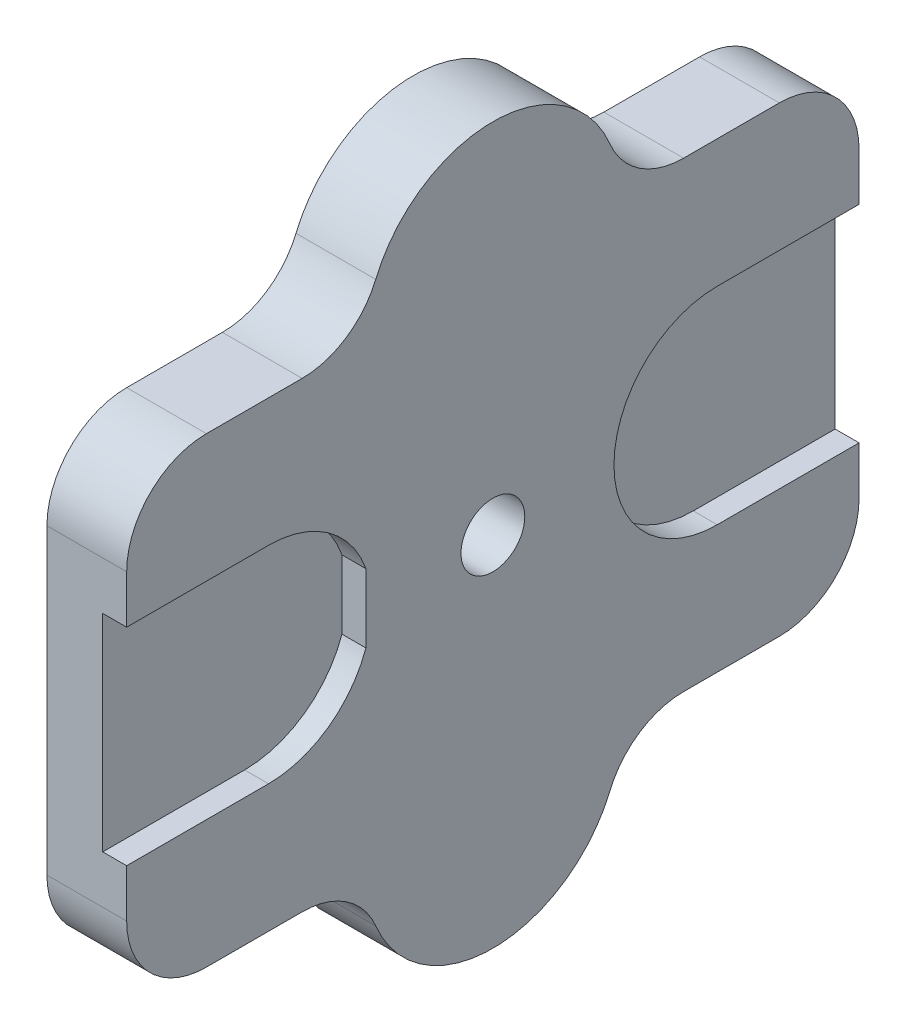
SolidWorks part; units mm, degrees
ref_plane "Front Plane" through (0, 0, 0) normal (1, 0, 0) x (0, 1, 0)
ref_plane "Top Plane" through (0, 0, 0) normal (0, 0, 1) x (0, 1, 0)
ref_plane "Right Plane" through (0, 0, 0) normal (0, 1, 0) x (-1, 0, 0)
sketch "Sketch1" plane through (0, 0, 0) normal (1, 0, 0) x (0, 1, 0)
  line L0 (-28.9545, 0) -> (33.8464, 0) construction
  line L3 (-28.9686, 19.054) -> (-28.9686, -12.7893) construction
  line L4 (0, 49.054) -> (0, -56.7378) construction
  line L6 (-28.9686, -12.7893) -> (28.9686, -12.7893)
  line L7 (44.5791, 0) -> (-44.5791, 0) construction
  line L9 (18.9686, 49.054) -> (-18.9686, 49.054)
  line L12 (-28.9686, 39.054) -> (-28.9686, 27.0474)
  line L13 (28.9686, 19.054) -> (28.9686, -12.7893) construction
  line L14 (28.9686, 39.054) -> (28.9686, 27.0474)
  line L15 (-28.9686, 19.054) -> (28.9686, 19.054) construction
  line L16 (-28.9686, 19.054) -> (28.9686, 19.054) construction
  arc A3 (-35.1108, 17.8215) -> (-28.9686, -12.7893) centre (-28.9686, 3.1323) ccw
  arc A4 (-18.9686, 49.054) -> (-28.9686, 39.054) centre (-18.9686, 39.054) ccw
  arc A5 (-35.1108, 17.8215) -> (-28.9686, 27.0474) centre (-38.9686, 27.0474) ccw
  arc A6 (35.1108, 17.8215) -> (28.9686, 27.0474) centre (38.9686, 27.0474) cw
  arc A7 (18.9686, 49.054) -> (28.9686, 39.054) centre (18.9686, 39.054) cw
  arc A8 (35.1108, 17.8215) -> (28.9686, -12.7893) centre (28.9686, 3.1323) cw
  point P20 (0, 0)
  dimension "D1" = 10
  dimension "D2" = 10
extrude "Boss-Extrude3" add sketch "Sketch1" along normal blind 10
sketch "Sketch3" plane through (10, 0, 0) normal (1, 0, 0) x (0, 1, 0)
  line L0 (-44.8903, 3.1323) -> (44.8903, 3.1323) construction
  line L2 (-28.9686, -12.7893) -> (28.9686, -12.7893) construction
  line L3 (0, -12.7893) -> (0, 49.054) construction
  line L4 (18.9686, 49.054) -> (-18.9686, 49.054) construction
  arc A3 (-35.1108, 17.8215) -> (-28.9686, -12.7893) centre (-28.9686, 3.1323) ccw construction
  arc A4 (28.9686, -12.7893) -> (35.1108, 17.8215) centre (28.9686, 3.1323) ccw construction
  circle A5 centre (0, 3.1323) radius 4
extrude "Cut-Extrude3" cut sketch "Sketch3" against normal blind 14.0462
sketch "Sketch4" plane through (10, 0, 0) normal (1, 0, 0) x (0, 1, 0)
  line L0 (-12.95, 49.054) -> (-12.95, 31.2677)
  line L4 (18.9686, 49.054) -> (-18.9686, 49.054) construction
  line L6 (0, 7.1323) -> (0, 31.2677) construction
  line L7 (12.95, 31.2677) -> (12.95, 49.054)
  line L8 (-12.95, 49.054) -> (12.95, 49.054)
  circle A1 centre (0, 3.1323) radius 4 construction
  circle A2 centre (0, 31.2677) radius 12.95 construction
  arc A3 (-12.95, 31.2677) -> (12.95, 31.2677) centre (0, 31.2677) ccw
extrude "Cut-Extrude4" cut sketch "Sketch4" against normal blind 3
sketch "Sketch5" plane through (10, 0, 0) normal (1, 0, 0) x (0, 1, 0)
  line L0 (-4, 3.1323) -> (49996, 3.1323) construction
ref_plane "Plane1" through (0, 0, 3.1323) normal (0, 0, 1) x (0, 1, 0)
mirror "Mirror1" about plane through (0, 0, 3.1323) normal (0, 0, 1) of "Boss-Extrude3", "Cut-Extrude3", "Cut-Extrude4"
